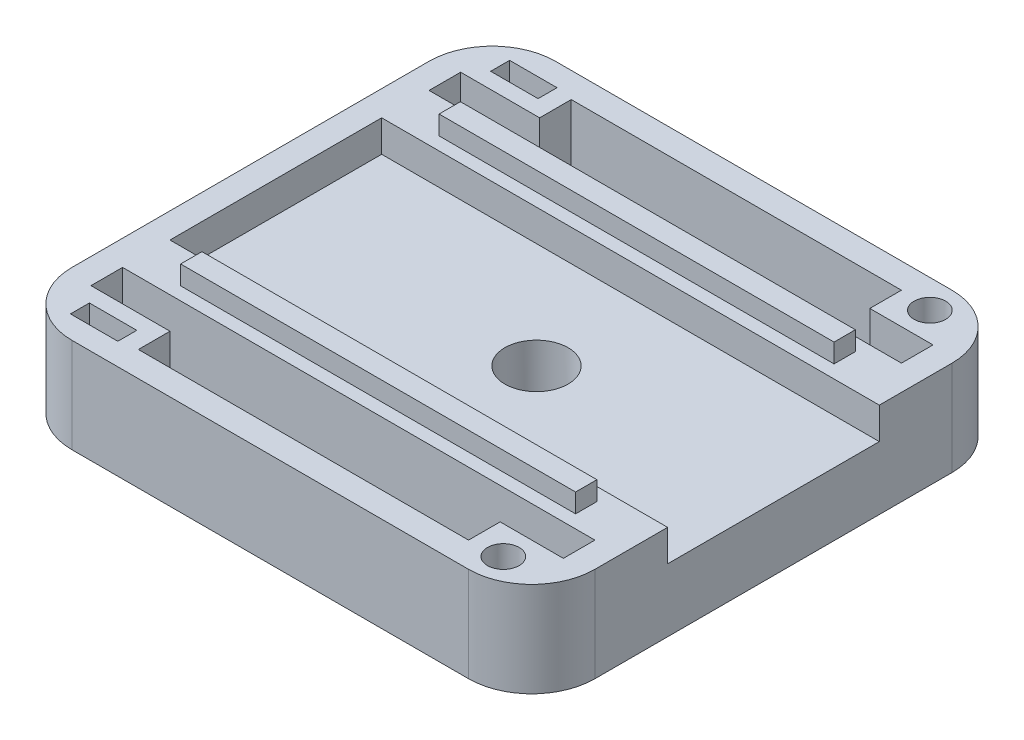
SolidWorks part; units mm, degrees
ref_plane "Front Plane" through (0, 0, 0) normal (0, 0, 1) x (1, 0, 0)
ref_plane "Top Plane" through (0, 0, 0) normal (0, 1, 0) x (1, 0, 0)
ref_plane "Right Plane" through (0, 0, 0) normal (1, 0, 0) x (0, 0, -1)
sketch "Sketch1" plane through (0, 0, 0) normal (0, 1, 0) x (1, 0, 0)
  line L1 (-42.037, -38.862) -> (42.037, -38.862)
  line L2 (-42.037, -38.862) -> (-42.037, 38.862)
  line L3 (-42.037, 38.862) -> (42.037, 38.862)
  line L4 (42.037, -38.862) -> (42.037, 38.862)
  line L5 (-42.037, -38.862) -> (42.037, 38.862) construction
  line L6 (-42.037, 38.862) -> (42.037, -38.862) construction
  point P0 (0, 0)
extrude "Boss-Extrude1" add sketch "Sketch1" along normal blind 5.08 and the other way blind 5.08
sketch "Sketch2" plane through (0, 5.08, 0) normal (0, 1, 0) x (1, 0, 0)
  line L0 (42.037, -38.862) -> (42.037, 38.862) construction
  line L1 (-42.037, 38.862) -> (42.037, 38.862)
  line L2 (-42.037, 38.862) -> (-42.037, 34.798)
  line L3 (-42.037, 34.798) -> (42.037, 34.798)
  line L4 (42.037, 38.862) -> (42.037, 34.798)
  line L6 (-42.037, -38.862) -> (42.037, -38.862)
  line L7 (-42.037, -38.862) -> (-42.037, -34.798)
  line L8 (-42.037, -34.798) -> (42.037, -34.798)
  line L9 (42.037, -38.862) -> (42.037, -34.798)
  line L10 (-42.037, 34.798) -> (-37.973, 34.798)
  line L11 (-42.037, 34.798) -> (-42.037, -34.798)
  line L12 (-42.037, -34.798) -> (-37.973, -34.798)
  line L13 (-37.973, 34.798) -> (-37.973, -34.798)
  line L14 (42.037, 34.798) -> (37.973, 34.798)
  line L15 (42.037, 34.798) -> (42.037, -34.798)
  line L16 (42.037, -34.798) -> (37.973, -34.798)
  line L17 (37.973, 34.798) -> (37.973, -34.798)
  line L18 (-37.973, 34.798) -> (-25.273, 34.798)
  line L19 (-37.973, 34.798) -> (-37.973, 29.718)
  line L20 (-37.973, 29.718) -> (-25.273, 29.718)
  line L21 (-25.273, 34.798) -> (-25.273, 29.718)
  line L22 (37.973, 34.798) -> (27.813, 34.798)
  line L23 (37.973, 34.798) -> (37.973, 29.718)
  line L24 (37.973, 29.718) -> (27.813, 29.718)
  line L25 (27.813, 34.798) -> (27.813, 29.718)
  line L26 (-37.973, -34.798) -> (-25.273, -34.798)
  line L27 (-37.973, -34.798) -> (-37.973, -29.718)
  line L28 (-37.973, -29.718) -> (-25.273, -29.718)
  line L29 (-25.273, -34.798) -> (-25.273, -29.718)
  line L30 (37.973, -34.798) -> (27.813, -34.798)
  line L31 (37.973, -34.798) -> (37.973, -29.718)
  line L32 (37.973, -29.718) -> (27.813, -29.718)
  line L33 (27.813, -34.798) -> (27.813, -29.718)
  dimension "D2" = 4.064
  dimension "D3" = 12.7
  dimension "D4" = 5.08
  dimension "D5" = 10.16
  dimension "D6" = 5.08
  dimension "D7" = 5.08
  dimension "D8" = 12.7
  dimension "D9" = 10.16
  dimension "D10" = 5.08
  dimension "D11" = 4.064
  dimension "D12" = 4.064
  dimension "D13" = 4.064
extrude "Boss-Extrude2" add sketch "Sketch2" along normal blind 5.08 and the other way blind 10.16 contours L21 L3 L15 L17 | L21 L3 L13 L20 | L13 L3 L21 L8 | L8 L29 L28 L13 | L8 L21 L20 L15 | L33 L8 L17 L32 | L3 L17 L8 L15 | L3 L25 L24 L17 region at (0, 5.08, -36.83) region at (-40.005, 5.08, 0) region at (40.005, 5.08, 0) region at (-31.623, 5.08, -32.258) region at (0, 5.08, 36.83) region at (32.893, 5.08, -32.258) region at (-31.623, 5.08, 32.258) region at (32.893, 5.08, 32.258)
sketch "Sketch3" plane through (0, 5.08, 0) normal (0, 1, 0) x (1, 0, 0)
  line L0 (27.813, 34.798) -> (27.813, 29.718) construction
  line L1 (-25.273, 34.798) -> (27.813, 34.798)
  line L2 (-25.273, 34.798) -> (-25.273, 29.718)
  line L3 (-25.273, 29.718) -> (27.813, 29.718)
  line L4 (27.813, 34.798) -> (27.813, 29.718)
  line L6 (27.813, -34.798) -> (27.813, -29.718) construction
  line L7 (-25.273, -34.798) -> (27.813, -34.798)
  line L8 (-25.273, -34.798) -> (-25.273, -29.718)
  line L9 (-25.273, -29.718) -> (27.813, -29.718)
  line L10 (27.813, -34.798) -> (27.813, -29.718)
  dimension "D1" = 5.08
  dimension "D2" = 5.08
extrude "Cut-Extrude1" cut sketch "Sketch3" against normal through all both and the other way through all
sketch "Sketch4" plane through (0, 5.08, 0) normal (0, 1, 0) x (1, 0, 0)
  line L0 (37.973, 29.718) -> (37.973, -29.718) construction
  line L1 (-37.973, 29.718) -> (37.973, 29.718)
  line L2 (-37.973, 29.718) -> (-37.973, 24.638)
  line L3 (-37.973, 24.638) -> (37.973, 24.638)
  line L4 (37.973, 29.718) -> (37.973, 24.638)
  line L6 (-37.973, -29.718) -> (37.973, -29.718)
  line L7 (-37.973, -29.718) -> (-37.973, -24.638)
  line L8 (-37.973, -24.638) -> (37.973, -24.638)
  line L9 (37.973, -29.718) -> (37.973, -24.638)
  dimension "D1" = 5.08
  dimension "D2" = 5.08
extrude "Cut-Extrude2" cut sketch "Sketch4" against normal through all both and the other way through all
sketch "Sketch5" plane through (0, 5.08, 0) normal (0, 1, 0) x (1, 0, 0)
  line L0 (37.973, 29.718) -> (37.973, -29.718) construction
  line L1 (-37.973, 24.638) -> (37.973, 24.638)
  line L2 (-37.973, 24.638) -> (-37.973, 17.018)
  line L3 (-37.973, 17.018) -> (37.973, 17.018)
  line L4 (37.973, 24.638) -> (37.973, 17.018)
  line L5 (37.973, 24.638) -> (37.973, -24.638) construction
  line L6 (-37.973, -24.638) -> (37.973, -24.638)
  line L7 (-37.973, -24.638) -> (-37.973, -17.018)
  line L8 (-37.973, -17.018) -> (37.973, -17.018)
  line L9 (37.973, -24.638) -> (37.973, -17.018)
  line L10 (-42.037, -38.862) -> (42.037, -38.862) construction
  line L11 (42.037, 38.862) -> (-42.037, 38.862) construction
  dimension "D1" = 14.224
  dimension "D2" = 21.844
  dimension "D3" = 14.224
  dimension "D4" = 21.844
extrude "Boss-Extrude3" add sketch "Sketch5" along normal blind 5.08 and the other way blind 10.16
sketch "Sketch7" plane through (37.973, 0, 0) normal (-1, 0, 0) x (0, 0, 1)
  line L1 (17.018, 10.16) -> (-17.018, 10.16)
  line L2 (17.018, 10.16) -> (17.018, 5.08)
  line L3 (17.018, 5.08) -> (-17.018, 5.08)
  line L4 (-17.018, 10.16) -> (-17.018, 5.08)
sketch "Sketch10" plane through (0, 5.08, 0) normal (0, 1, 0) x (1, 0, 0)
  line L0 (42.037, 17.018) -> (42.037, -17.018) construction
  circle A0 centre (3.937, 0) radius 5.08
  dimension "D1" = 38.1
extrude "Cut-Extrude4" cut sketch "Sketch10" against normal through all both and the other way through all
fillet "Fillet1" radius 10.16 4 edges at (42.037, 2.54, -38.862) (-42.037, 2.54, -38.862) (-42.037, 2.54, 38.862) (42.037, 2.54, 38.862)
sketch "Sketch14" plane through (0, 10.16, 0) normal (0, 1, 0) x (1, 0, 0)
  line L0 (37.973, 24.638) -> (-37.973, 24.638) construction
  line L1 (-30.7345, -22.5425) -> (32.7655, -22.5425)
  line L2 (-30.7345, -22.5425) -> (-30.7345, -19.1135)
  line L3 (-30.7345, -19.1135) -> (32.7655, -19.1135)
  line L4 (32.7655, -22.5425) -> (32.7655, -19.1135)
  line L5 (-30.7345, -22.5425) -> (32.7655, -19.1135) construction
  line L6 (-30.7345, -19.1135) -> (32.7655, -22.5425) construction
  line L7 (-30.8356, 19.1135) -> (32.6644, 19.1135)
  line L8 (-30.8356, 19.1135) -> (-30.8356, 22.5425)
  line L9 (-30.8356, 22.5425) -> (32.6644, 22.5425)
  line L10 (32.6644, 19.1135) -> (32.6644, 22.5425)
  line L11 (-30.8356, 19.1135) -> (32.6644, 22.5425) construction
  line L12 (-30.8356, 22.5425) -> (32.6644, 19.1135) construction
  line L13 (-37.973, -24.638) -> (37.973, -24.638) construction
  point P0 (1.0155, -20.828)
  point P5 (0.9144, 20.828)
  dimension "D1" = 3.81
  dimension "D2" = 3.81
extrude "Boss-Extrude7" add sketch "Sketch14" along normal blind 3.048
sketch "Sketch15" plane through (0, 10.16, 0) normal (0, 1, 0) x (1, 0, 0)
  line L0 (-42.037, 28.702) -> (-42.037, -28.702) construction
  line L1 (31.877, 38.862) -> (-31.877, 38.862) construction
  line L2 (42.037, -28.702) -> (42.037, 28.702) construction
  line L3 (-35.687, 32.258) -> (-28.067, 32.258)
  line L4 (-35.687, 32.258) -> (-35.687, 35.306)
  line L5 (-35.687, 35.306) -> (-28.067, 35.306)
  line L6 (-28.067, 32.258) -> (-28.067, 35.306)
  line L7 (-35.687, 32.258) -> (-28.067, 35.306) construction
  line L8 (-35.687, 35.306) -> (-28.067, 32.258) construction
  circle A0 centre (32.893, 34.29) radius 2.54
  point P0 (-31.877, 33.782)
  point P5 (-31.877, 33.782)
  dimension "D3" = 9.144
  dimension "D1" = 10.16
  dimension "D2" = 5.08
  dimension "D4" = 4.572
extrude "Cut-Extrude6" cut sketch "Sketch15" against normal through all both and the other way through all
mirror "Mirror1" about plane through (0, 0, 0) normal (0, 0, 1) of "Cut-Extrude6"
extrude "Cut-Extrude7" cut sketch "Sketch7" against normal through all
